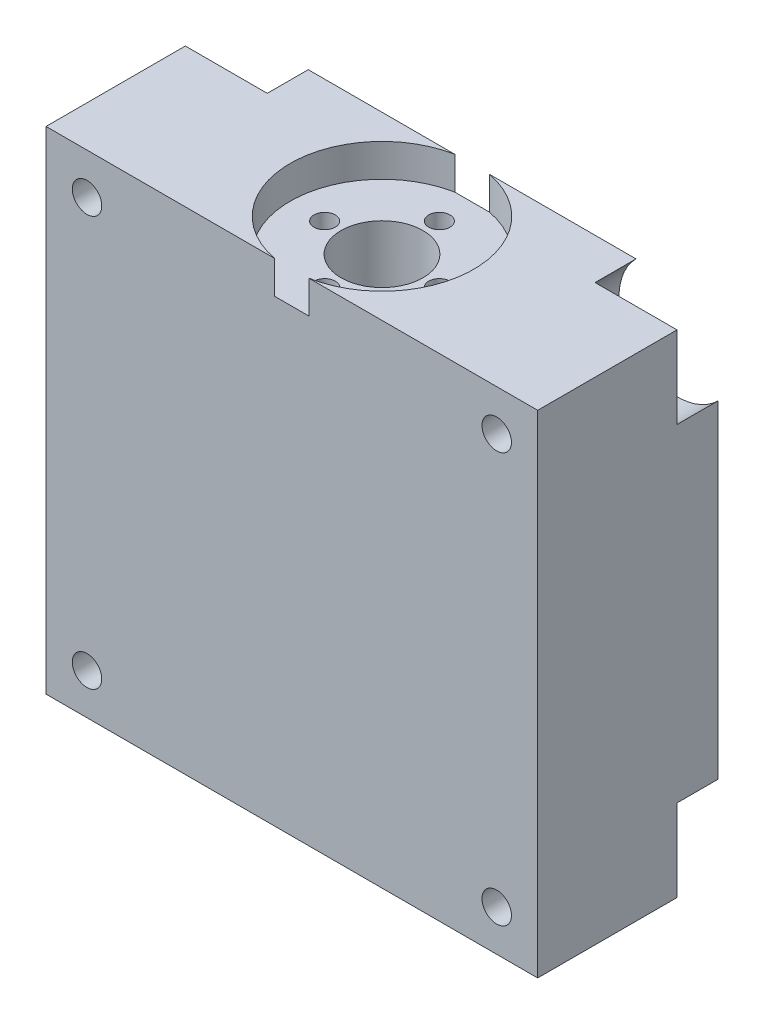
SolidWorks part; units mm, degrees
ref_plane "Front Plane" through (0, 0, 0) normal (0, 0, 1) x (1, 0, 0)
ref_plane "Top Plane" through (0, 0, 0) normal (0, 1, 0) x (1, 0, 0)
ref_plane "Right Plane" through (0, 0, 0) normal (1, 0, 0) x (0, 0, -1)
sketch "Sketch1" plane through (0, 0, 0) normal (0, 0, 1) x (1, 0, 0)
  line L1 (-30, 30) -> (30, 30)
  line L2 (-30, 30) -> (-30, -30)
  line L3 (-30, -30) -> (30, -30)
  line L4 (30, 30) -> (30, -30)
  line L5 (-30, 30) -> (30, -30) construction
  line L6 (-30, -30) -> (30, 30) construction
  line L7 (-25, -25) -> (25, -25) construction
  line L8 (-25, -25) -> (-25, 25) construction
  line L9 (-25, 25) -> (25, 25) construction
  line L10 (25, -25) -> (25, 25) construction
  line L11 (-25, -25) -> (25, 25) construction
  line L12 (-25, 25) -> (25, -25) construction
  circle A0 centre (-25, 25) radius 1.8
  circle A1 centre (25, 25) radius 1.8
  circle A2 centre (25, -25) radius 1.8
  circle A3 centre (-25, -25) radius 1.8
  point P0 (0, 0)
  point P6 (0, 0)
  dimension "D1" = 60
  dimension "D2" = 60
  dimension "D3" = 50
  dimension "D4" = 50
extrude "Boss-Extrude1" add sketch "Sketch1" along normal blind 22
sketch "Sketch2" plane through (0, 30, 0) normal (0, 1, 0) x (1, 0, 0)
  line L0 (30, 0) -> (-30, 0) construction
  circle A0 centre (0, -11) radius 11.2
  dimension "D1" = 11
extrude "Cut-Extrude1" cut sketch "Sketch2" against normal blind 4
sketch "Sketch3" plane through (0, 26, 0) normal (0, 1, 0) x (1, 0, 0)
  circle A0 centre (0, -11) radius 5
extrude "Cut-Extrude2" cut sketch "Sketch3" against normal up to next
sketch "Sketch4" plane through (0, -30, 0) normal (0, -1, 0) x (1, 0, 0)
  circle A0 centre (0, 11) radius 7.2
extrude "Cut-Extrude3" cut sketch "Sketch4" against normal blind 46
sketch "Sketch5" plane through (0, 26, 0) normal (0, 1, 0) x (1, 0, 0)
  circle A0 centre (0, -11) radius 7 construction
  circle A1 centre (0, -4) radius 1.3
  circle A2 centre (7, -11) radius 1.3
  circle A3 centre (0, -18) radius 1.3
  circle A4 centre (-7, -11) radius 1.3
extrude "Cut-Extrude4" cut sketch "Sketch5" against normal blind 6
sketch "Sketch6" plane through (0, 0, 0) normal (0, 0, -1) x (-1, 0, 0)
  circle A0 centre (-25, 25) radius 7.0711
  circle A1 centre (25, 25) radius 7.0711
  circle A2 centre (25, -25) radius 7.0711
  circle A3 centre (-25, -25) radius 7.0711
extrude "Cut-Extrude5" cut sketch "Sketch6" against normal blind 5
